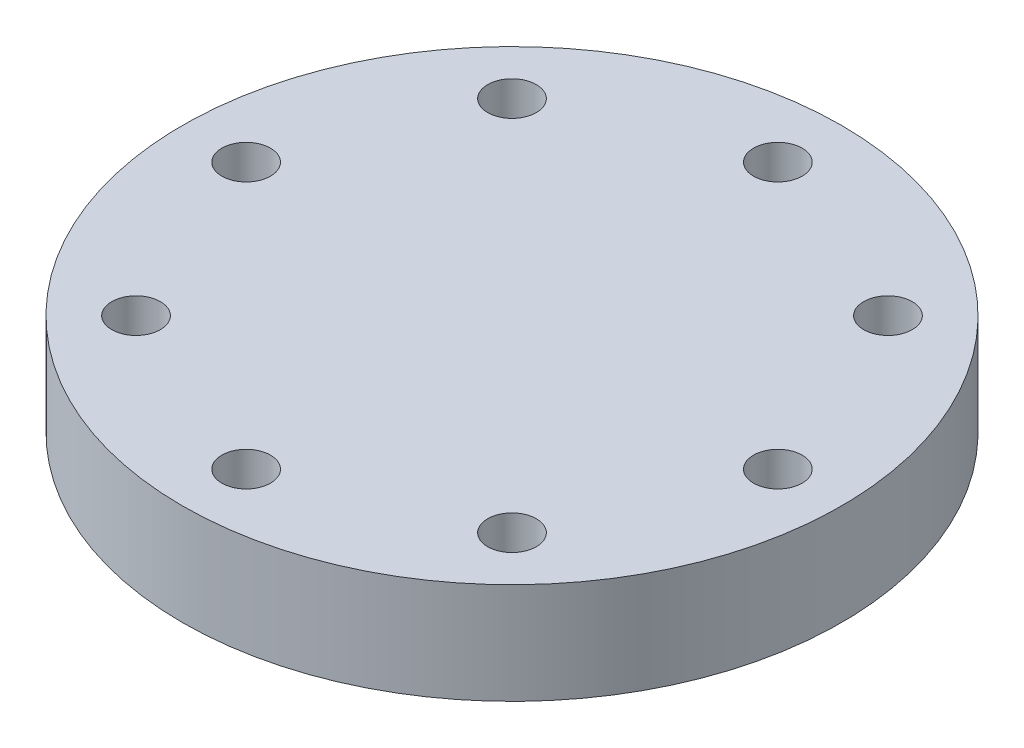
SolidWorks part; units mm, degrees
ref_plane "Front Plane" through (0, 0, 0) normal (0, 0, 1) x (1, 0, 0)
ref_plane "Top Plane" through (0, 0, 0) normal (0, 1, 0) x (1, 0, 0)
ref_plane "Right Plane" through (0, 0, 0) normal (1, 0, 0) x (0, 0, -1)
sketch "Sketch1" plane through (0, 0, 0) normal (0, 1, 0) x (1, 0, 0)
  circle A0 centre (0, 0) radius 57.15
  dimension "D1" = 114.3
extrude "Extrude1" add sketch "Sketch1" along normal blind 17.526
sketch "Sketch2" plane through (0, 0, 0) normal (0, 1, 0) x (1, 0, 0)
  circle A0 centre (0, 46.101) radius 4.2164
extrude "Cut-Extrude2" cut sketch "Sketch2" along normal blind 17.526
ref_axis "Axis1" through (0, 58.677, 0) along (0, -1, 0)
pattern_circular "CirPattern1" count 8 over 360 about axis through (0, 58.677, 0) along (0, -1, 0) of "Cut-Extrude2"
sketch "Sketch4" plane through (0, 0, 0) normal (0, 1, 0) x (1, 0, 0)
  line L0 (0, 0) -> (0, 46.8507)
